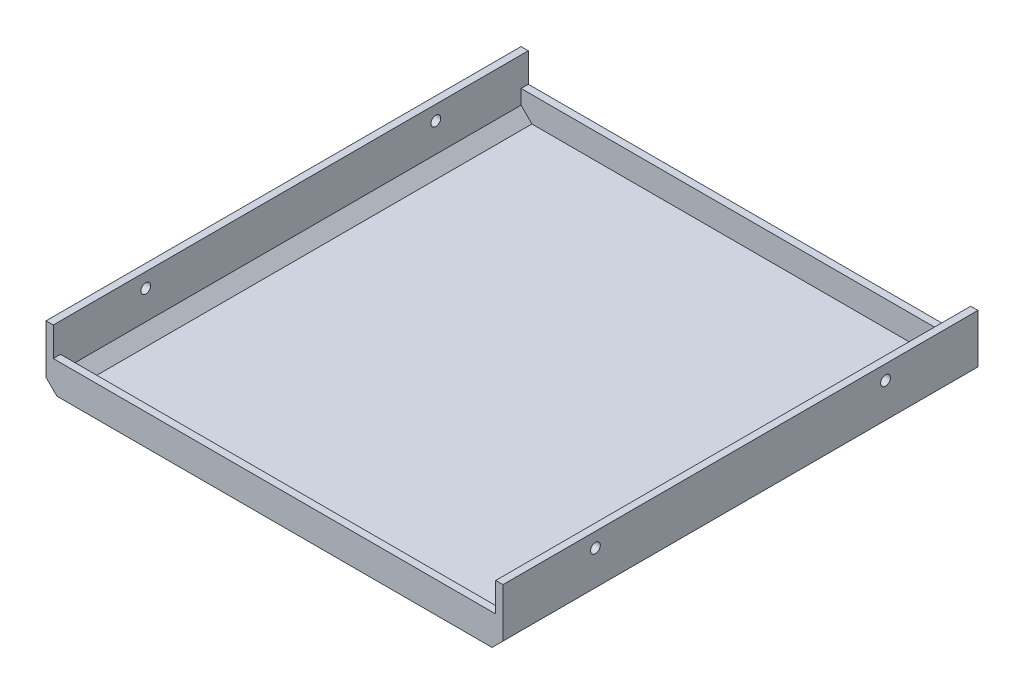
SolidWorks part; units mm, degrees
ref_plane "Front Plane" through (0, 0, 0) normal (0, 0, 1) x (1, 0, 0)
ref_plane "Top Plane" through (0, 0, 0) normal (0, 1, 0) x (1, 0, 0)
ref_plane "Right Plane" through (0, 0, 0) normal (1, 0, 0) x (0, 0, -1)
sketch "Sketch1" plane through (0, 0, 0) normal (0, 1, 0) x (1, 0, 0)
  line L0 (0, 74.5) -> (0, -74.5) construction
  line L1 (0, -74.5) -> (65, -74.5) construction
  line L2 (-63, 66.5) -> (63, 66.5)
  line L3 (-63, 66.5) -> (-63, -64.5)
  line L4 (-63, -64.5) -> (63, -64.5)
  line L5 (63, 66.5) -> (63, -64.5)
  dimension "D1" = 65
  dimension "D2" = 131
  dimension "D3" = 126
extrude "Boss-Extrude1" add sketch "Sketch1" along normal blind 1.5
sketch "Sketch2" plane through (0, 1.5, 0) normal (0, 1, 0) x (1, 0, 0)
  line L0 (-63, -64.5) -> (63, -64.5) construction
  line L1 (-63, 66.5) -> (-61, 66.5)
  line L2 (-63, 66.5) -> (-63, -64.5)
  line L3 (-63, -64.5) -> (-61, -64.5)
  line L4 (-61, 66.5) -> (-61, -64.5)
  line L5 (63, 66.5) -> (-63, 66.5) construction
  line L6 (63, -64.5) -> (61, -64.5)
  line L7 (63, -64.5) -> (63, 66.5)
  line L8 (63, 66.5) -> (61, 66.5)
  line L9 (61, -64.5) -> (61, 66.5)
  dimension "D1" = 2
  dimension "D2" = 2
extrude "Boss-Extrude2" add sketch "Sketch2" along normal blind 15
sketch "Sketch3" plane through (-63, 0, 0) normal (-1, 0, 0) x (0, 0, 1)
  line L0 (-1, 16.5) -> (-1, 12.5) construction
  line L1 (-66.5, 16.5) -> (64.5, 16.5) construction
  line L2 (-1, 12.5) -> (-41, 12.5) construction
  circle A0 centre (-41, 12.5) radius 1.35
  circle A1 centre (39, 12.5) radius 1.35
  dimension "D1" = 4
  dimension "D2" = 40
extrude "Cut-Extrude1" cut sketch "Sketch3" against normal up to surface (126 mm away) up to face at (63, 8.25, -1)
sketch "Sketch5" plane through (0, 1.5, 0) normal (0, 1, 0) x (1, 0, 0)
  line L0 (61, 66.5) -> (61, -64.5) construction
  line L1 (-61, 66.5) -> (61, 66.5)
  line L2 (-61, 66.5) -> (-61, 64.5)
  line L3 (-61, 64.5) -> (61, 64.5)
  line L4 (61, 66.5) -> (61, 64.5)
  line L5 (-61, -64.5) -> (-61, 66.5) construction
  line L6 (61, -64.5) -> (-61, -64.5)
  line L7 (61, -64.5) -> (61, -62.5)
  line L8 (61, -62.5) -> (-61, -62.5)
  line L9 (-61, -64.5) -> (-61, -62.5)
  dimension "D1" = 2
  dimension "D2" = 2
extrude "Boss-Extrude3" add sketch "Sketch5" along normal blind 7
chamfer "Chamfer3" distance 3 angle 45 2 edges at (-63, 0, -1) (63, 0, -1)
chamfer "Chamfer1" distance 3 angle 45 2 edges at (61, 1.5, -1) (-61, 1.5, -1)
chamfer "Chamfer2" distance 3 angle 45 rebuild error yes
